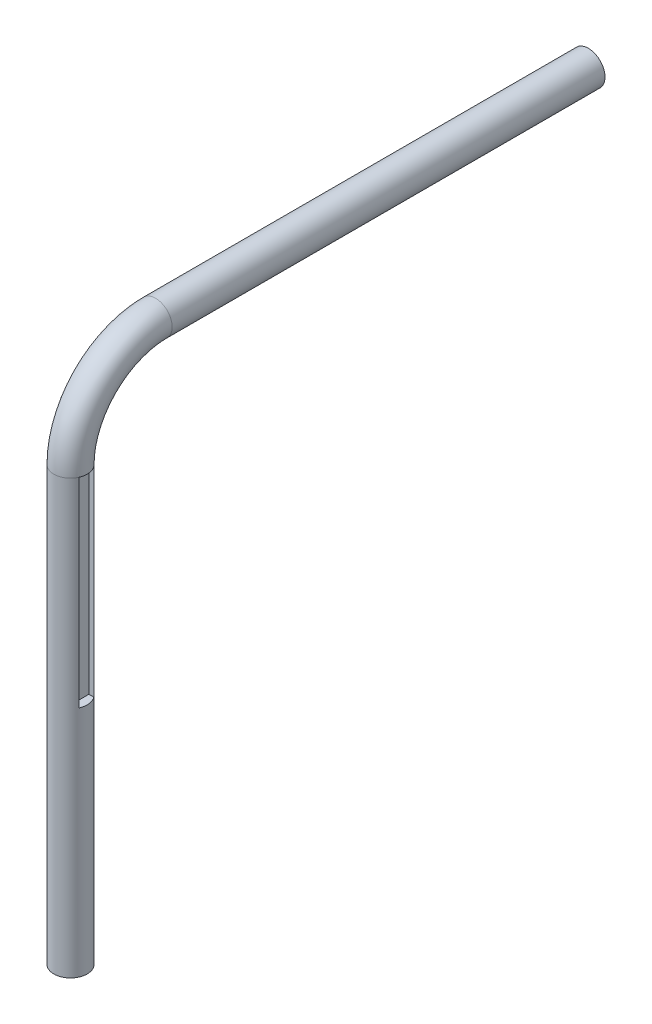
SolidWorks part; units mm, degrees
material "Cast Carbon Steel"
ref_plane "Front Plane" through (0, 0, 0) normal (0, 0, 1) x (1, 0, 0)
ref_plane "Top Plane" through (0, 0, 0) normal (0, 1, 0) x (1, 0, 0)
ref_plane "Right Plane" through (0, 0, 0) normal (1, 0, 0) x (0, 0, -1)
sketch "Sketch2" plane through (0, 0, 0) normal (1, 0, 0) x (0, 0, -1)
  arc A0 (-64.8338, 0) -> (0, 64.8338) centre (0, 0) cw
  dimension "D1" = 64.8338
sketch "Sketch3" plane through (0, 0, 0) normal (0, 1, 0) x (1, 0, 0)
  circle A0 centre (0, -64.8338) radius 12.7
  circle A1 centre (0, -64.8338) radius 4.7625
  dimension "D1" = 25.4
  dimension "D2" = 7.9375
sweep "Sweep1" add profiles "Sketch3" path "Sketch2"
ref_plane "Plane1" through (0, 0, 0) normal (0, -1, 0) x (-1, 0, 0)
ref_plane "Plane2" through (0, 0, 0) normal (0, 0, -1) x (-1, 0, 0)
sketch "Sketch4" plane through (0, 0, 0) normal (0, -1, 0) x (-1, 0, 0)
  circle A0 centre (0, -64.8338) radius 12.7
  circle A1 centre (0, -64.8338) radius 4.7625
  dimension "D1" = 7.9375
  dimension "D2" = 25.4
  dimension "D3" = 64.8338
extrude "Boss-Extrude3" add sketch "Sketch4" along normal blind 330.2
sketch "Sketch5" plane through (0, 0, 0) normal (0, 0, -1) x (-1, 0, 0)
  circle A0 centre (0, 64.8338) radius 12.7
  circle A1 centre (0, 64.8338) radius 4.7625
  dimension "D1" = 7.9375
  dimension "D2" = 25.4
  dimension "D3" = 64.8338
extrude "Boss-Extrude4" add sketch "Sketch5" along normal blind 330.2
ref_plane "Plane3" through (-12.7, 0, 0) normal (-1, 0, 0) x (0, 0, 1)
ref_plane "Plane4" through (12.7, 0, 0) normal (1, 0, 0) x (0, 0, -1)
sketch "Sketch7" plane through (12.7, 0, 0) normal (1, 0, 0) x (0, 0, -1)
  line L0 (0, -13.97) -> (0, 13.97) construction
  line L1 (-69.85, 0) -> (-57.15, 0)
  line L2 (-69.85, 0) -> (-69.85, -152.4)
  line L3 (-69.85, -152.4) -> (-57.15, -152.4)
  line L4 (-57.15, 0) -> (-57.15, -152.4)
  line L5 (-52.1338, 0) -> (-77.5338, 0) construction
  point P9 (-63.5, -152.4)
  dimension "D1" = 12.7
  dimension "D2" = 152.4
  dimension "D3" = 57.15
  dimension "D4" = 63.5
extrude "Cut-Extrude2" cut sketch "Sketch7" against normal blind 6.35
